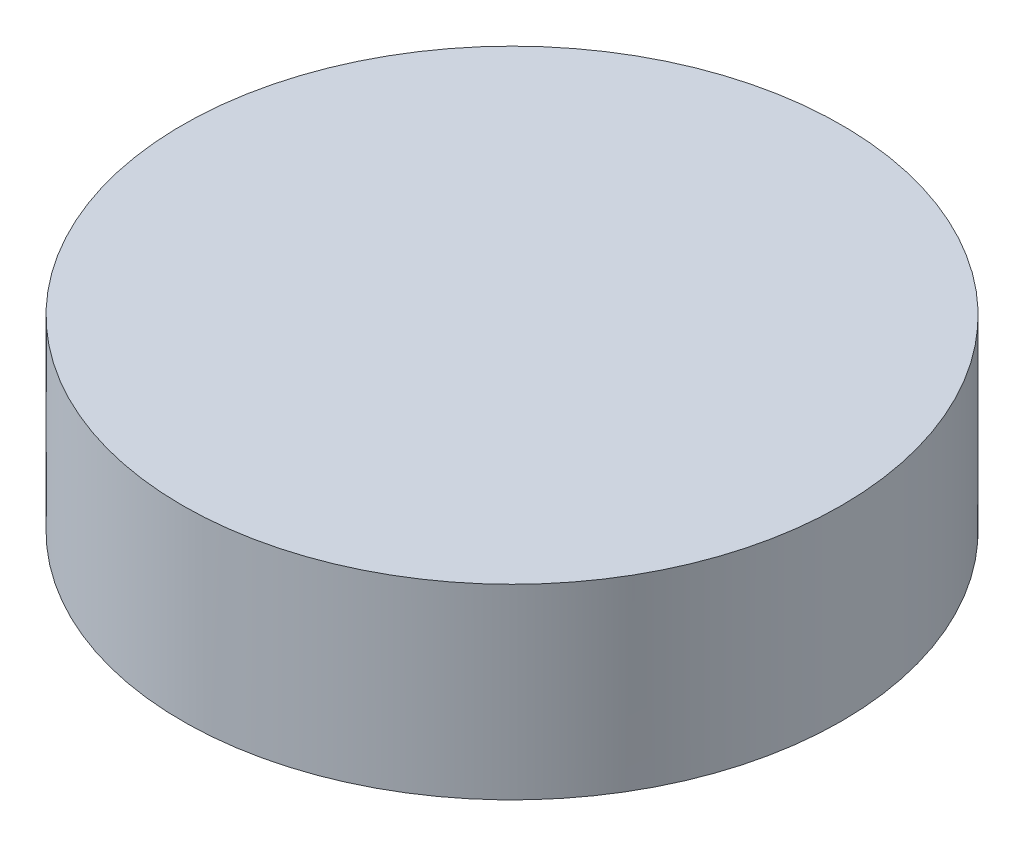
SolidWorks part; units mm, degrees
ref_plane "Front Plane" through (0, 0, 0) normal (0, 0, 1) x (1, 0, 0)
ref_plane "Top Plane" through (0, 0, 0) normal (0, 1, 0) x (1, 0, 0)
ref_plane "Right Plane" through (0, 0, 0) normal (1, 0, 0) x (0, 0, -1)
sketch "Sketch1" plane through (0, 7.5, 0) normal (0, 1, 0) x (1, 0, 0)
  circle A0 centre (0, 0) radius 15
extrude "Boss-Extrude1" add sketch "Sketch1" along normal blind 1
sketch "Sketch2" plane through (0, 7.5, 0) normal (0, -1, 0) x (1, 0, 0)
  circle A0 centre (0, 0) radius 14
extrude "Extrude-Thin1" add sketch "Sketch2" along normal blind 7.5 thin
thread "Thread1" pitch 2 start angle 0, offset 0, length 0, pitch 2, diameter 28
ref_plane "Plane1" through (14, 0, 0) normal (0, 0, 1) x (1, 0, 0)
sketch "Thread Profile1" plane through (14, 0, 0) normal (0, 0, 1) x (1, 0, 0)
  line L0 (0, 0) -> (0, 2) construction
  line L11 (0, 0) -> (0, 1.75)
  line L12 (0, 1.75) -> (-1.0825, 1.125)
  line L13 (-1.0825, 1.125) -> (-1.0825, 0.625)
  line L15 (-1.0825, 0.625) -> (0, 0)
  line L17 (-1.0825, 0.875) -> (0, 0.875) construction
  point P2 (0, 0)
  dimension "Pitch" = 2
  dimension "Profile_Angle" = 60
  dimension "Profile_Land" = 0.5
  dimension "Profile_Height" = 1.0825
